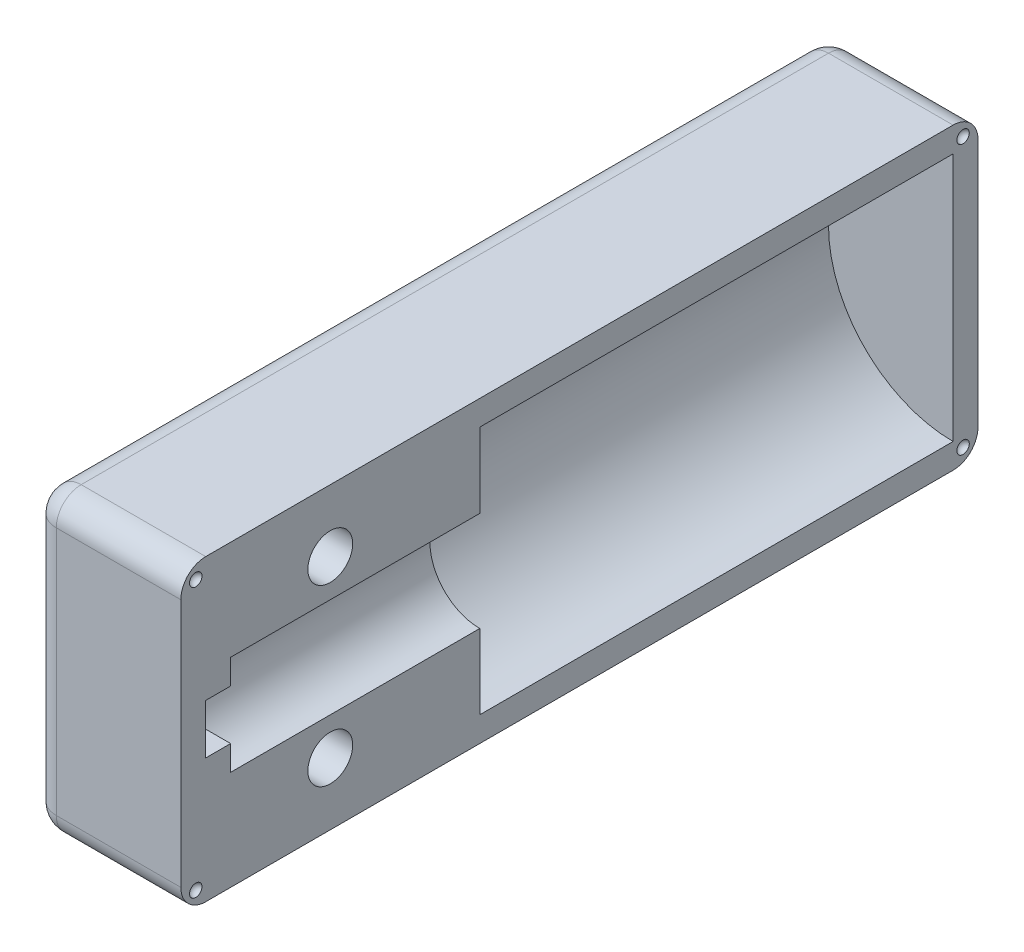
SolidWorks part; units mm, degrees
ref_plane "正面" through (0, 0, 0) normal (0, 0, 1) x (1, 0, 0)
ref_plane "平面" through (0, 0, 0) normal (0, 1, 0) x (1, 0, 0)
ref_plane "右側面" through (0, 0, 0) normal (1, 0, 0) x (0, 0, -1)
sketch "Sketch1" plane through (0, 0, 0) normal (0, 0, 1) x (1, 0, 0)
  line L1 (0, 0) -> (6, 0)
  line L2 (0, 0) -> (0, 12)
  line L3 (0, 12) -> (6, 12)
  line L4 (6, 0) -> (6, 12)
  dimension "D1" = 12
  dimension "D2" = 6
extrude "Boss-Extrude1" add sketch "Sketch1" against normal blind 20 contours L3 L4 L1 L2
sketch "Sketch2" plane through (0, 0, 0) normal (0, 0, 1) x (1, 0, 0)
  line L0 (6, 0) -> (6, 12) construction
  circle A0 centre (6, 6) radius 5
  dimension "D1" = 10
extrude "Cut-Extrude1" cut sketch "Sketch2" against normal blind 19
sketch "Sketch6" plane through (0, 0, 0) normal (0, 0, 1) x (1, 0, 0)
  line L0 (0, 0) -> (6, 0) construction
  line L1 (6, 12) -> (0, 12)
  line L2 (6, 12) -> (6, 0)
  line L3 (6, 0) -> (0, 0)
  line L4 (0, 12) -> (0, 0)
  line L9 (0, 0) -> (0, 12) construction
extrude "Boss-Extrude3" add sketch "Sketch6" along normal blind 12
sketch "Sketch7" plane through (0, 0, 0) normal (0, 0, -1) x (-1, 0, 0)
  line L0 (-6, 0) -> (-6, 12) construction
  circle A0 centre (-6, 6) radius 2
  dimension "D1" = 4
extrude "Cut-Extrude2" cut sketch "Sketch7" against normal blind 10
sketch "Sketch8" plane through (0, 0, 0) normal (-1, 0, 0) x (0, 0, 1)
  line L0 (12, 12) -> (12, 0) construction
  line L1 (10, 7) -> (11, 7)
  line L2 (10, 7) -> (10, 5)
  line L3 (10, 5) -> (11, 5)
  line L4 (11, 7) -> (11, 5)
  line L5 (12, 12) -> (-20, 12) construction
  dimension "D1" = 1
  dimension "D2" = 1
  dimension "D3" = 2
  dimension "D4" = 5
extrude "Cut-Extrude3" cut sketch "Sketch8" against normal through all and the other way through all
fillet "Fillet1" radius 1 8 edges at (0, 0, -4) (0, 6, 12) (0, 12, -4) (0, 6, -20) (3, 0, 12) (3, 12, 12) (3, 0, -20) (3, 12, -20)
sketch "Sketch10" plane through (6, 0, 0) normal (1, 0, 0) x (0, 0, -1)
  line L0 (0, 8) -> (0, 11) construction
  line L1 (19, 12) -> (-11, 12) construction
  circle A0 centre (-6, 9.5) radius 0.9
  dimension "D1" = 1.8
  dimension "D2" = 6
  dimension "D3" = 2.5
extrude "Cut-Extrude4" cut sketch "Sketch10" against normal blind 10
sketch "Sketch12" plane through (0, 0, 0) normal (-1, 0, 0) x (0, 0, 1)
  line L0 (-19, 12) -> (11, 12) construction
  line L1 (6.9238, 7.9) -> (7.8475, 9.5)
  line L2 (7.8475, 9.5) -> (6.9238, 11.1)
  line L3 (6.9238, 11.1) -> (5.0762, 11.1)
  line L4 (5.0762, 11.1) -> (4.1525, 9.5)
  line L5 (4.1525, 9.5) -> (5.0762, 7.9)
  line L6 (5.0762, 7.9) -> (6.9238, 7.9)
  circle A0 centre (6, 9.5) radius 1.6 construction
  dimension "D1" = 3.2
extrude "Cut-Extrude5" cut sketch "Sketch12" against normal blind 2
ref_plane "Plane1" through (0, 6, 0) normal (0, 1, 0) x (1, 0, 0)
mirror "Mirror1" about plane through (0, 6, 0) normal (0, 1, 0) of "Cut-Extrude5", "Cut-Extrude4"
ref_plane "Plane2" through (0, 0, -19.4) normal (0, 0, -1) x (-1, 0, 0)
sketch "Sketch11" plane through (0, 0, -19.4) normal (0, 0, -1) x (-1, 0, 0)
  line L0 (-6, 1) -> (-6, 11) construction
  line L1 (-6, 12) -> (-1, 12) construction
  line L2 (-5.75, 11.4) -> (-6, 11.4)
  line L3 (-6, 11.4) -> (-6, 11.15)
  arc A0 (-6, 11.15) -> (-5.75, 11.4) centre (-6, 11.4) ccw
  dimension "D2" = 0.5
  dimension "D1" = 0.6
revolve "Cut-Revolve1" cut sketch "Sketch11" angle 360 about L2
ref_plane "Plane3" through (0, 0, -4) normal (0, 0, 1) x (1, 0, 0)
mirror "Mirror2" about plane through (0, 6, 0) normal (0, 1, 0) of "Cut-Revolve1" second plane through (0, 0, -4) second plane normal (0, 0, 1)
